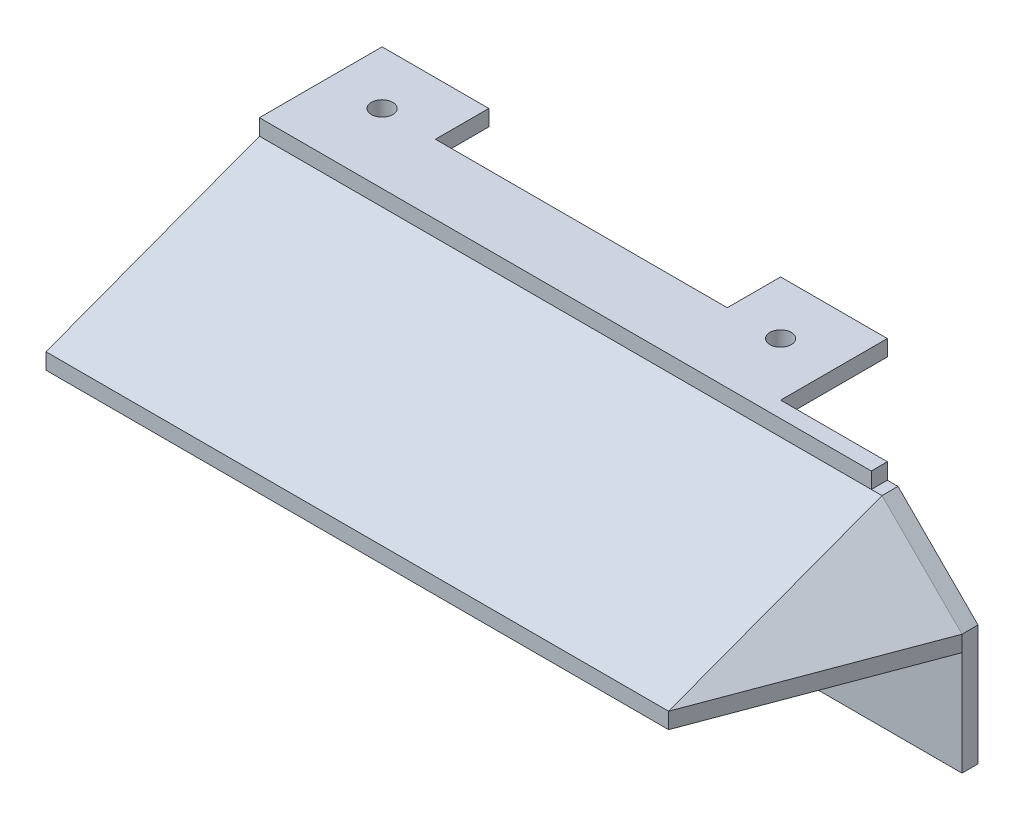
SolidWorks part; units mm, degrees
ref_plane "Plan de face" through (0, 0, 0) normal (0, 0, 1) x (1, 0, 0)
ref_plane "Plan de dessus" through (0, 0, 0) normal (0, 1, 0) x (1, 0, 0)
ref_plane "Plan de droite" through (0, 0, 0) normal (1, 0, 0) x (0, 0, -1)
sketch "Esquisse1" plane through (0, 0, 0) normal (0, 1, 0) x (1, 0, 0)
  line L0 (-37.6864, 50.2162) -> (-27.6864, 50.2162)
  line L1 (-27.6864, 50.2162) -> (-27.6864, 40.2162)
  line L2 (-27.6864, 40.2162) -> (-137.6864, 40.2162)
  line L3 (-37.6864, 50.2162) -> (-137.6864, 50.2162)
  line L4 (-137.6864, 50.2162) -> (-137.6864, 40.2162)
  line L5 (-137.6864, 50.2162) -> (-117.6864, 50.2162)
  line L6 (-122.3907, 50.2162) -> (-122.3907, 40.2162)
extrude "Boss.-Extru.1" add sketch "Esquisse1" along normal blind 3 contours L3 L6 L2 L1 L0 region at (-75.0386, 0, -45.2162)
sketch "Esquisse2" plane through (0, 0, -50.2162) normal (0, 0, -1) x (-1, 0, 0)
  line L0 (27.6864, 0) -> (27.6864, 3)
  line L1 (27.6864, 0) -> (47.6864, 0)
  line L2 (27.6864, 3) -> (47.6864, 3)
  line L3 (47.6864, 0) -> (47.6864, 3)
extrude "Boss.-Extru.2" add sketch "Esquisse2" along normal blind 10
sketch "Esquisse3" plane through (0, 3, 0) normal (0, 1, 0) x (1, 0, 0)
  line L0 (-27.6864, 50.2162) -> (-37.6864, 50.2162)
  line L1 (-27.6864, 40.2162) -> (-27.6864, 60.2162) construction
  circle A0 centre (-37.6864, 50.2162) radius 2
extrude "Enlèv. mat.-Extru.1" cut sketch "Esquisse3" against normal blind 10 contours A0 region at (-39.6298, 3, -50.2162)
sketch "Esquisse4" plane through (0, 0, -50.2162) normal (0, 0, -1) x (-1, 0, 0)
  line L0 (122.3907, 0) -> (102.3907, 0)
  line L1 (47.6864, 0) -> (122.3907, 0) construction
  line L2 (102.3907, 0) -> (102.3907, 3)
  line L3 (47.6864, 3) -> (122.3907, 3) construction
  line L4 (102.3907, 3) -> (122.3907, 3)
  line L5 (122.3907, 3) -> (122.3907, 0) construction
  line L6 (122.3907, 3) -> (122.3907, 0)
extrude "Boss.-Extru.3" add sketch "Esquisse4" along normal blind 10
sketch "Esquisse5" plane through (0, 3, 0) normal (0, 1, 0) x (1, 0, 0)
  line L0 (-102.3907, 50.2162) -> (-112.3907, 50.2162)
  circle A0 centre (-112.3907, 50.2162) radius 2
extrude "Enlèv. mat.-Extru.2" cut sketch "Esquisse5" against normal blind 20 contours A0 region at (-114.3342, 3, -50.2162)
sketch "Esquisse6" plane through (0, 0, -40.2162) normal (0, 0, 1) x (1, 0, 0)
  line L0 (-27.6864, 3) -> (-7.6864, 3)
  line L1 (-7.6864, 3) -> (-7.6864, 0)
  line L2 (-7.6864, 0) -> (-27.6864, 0)
  line L3 (-27.6864, 0) -> (-122.3907, 0)
  line L4 (-122.3907, 0) -> (-122.3907, 3)
  line L5 (-122.3907, 3) -> (-27.6864, 3)
  line L6 (-7.6864, 3) -> (-5.6864, 3)
  line L7 (-7.6864, 0) -> (-5.6864, 0)
  line L8 (-5.6864, 0) -> (-5.6864, 3)
  line L9 (-5.6864, 0) -> (9.3113, -14.9977)
  line L10 (9.3113, -14.9977) -> (9.3113, -37.5577)
  line L11 (9.3113, -37.5577) -> (-122.3907, -37.5577)
  line L12 (-122.3907, -37.5577) -> (-122.3907, 0)
  line L13 (-122.3907, 0) -> (-27.6864, 0)
  line M7 (-122.3907, 0) -> (-27.6864, 0)
  line M8 (-27.6864, 0) -> (-27.6864, 3)
  line M9 (-27.6864, 3) -> (-122.3907, 3)
  line M10 (-122.3907, 3) -> (-122.3907, 0)
extrude "Boss.-Extru.4" add sketch "Esquisse6" along normal blind 3 contours M10 M7 M8 M9 | L12 L11 L10 L9 L7 L2 M7 | L2 L1 L0 M8 region at (-75.0386, 1.5, -40.2162) region at (-17.6864, 1.5, -40.2162) region at (-57.9555, -19.0995, -40.2162)
sketch "Esquisse7" plane through (0, 0, -37.2162) normal (0, 0, 1) x (1, 0, 0)
  line L0 (9.3113, -14.9977) -> (9.3113, -17.9977)
  line L1 (9.3113, -14.9977) -> (9.3113, -37.5577) construction
  line L2 (9.3113, -17.9977) -> (-122.3907, -17.9977)
  line L3 (-122.3907, 3) -> (-122.3907, -37.5577) construction
  line L4 (-122.3907, -17.9977) -> (-122.3907, -16.4977)
  line L5 (-122.3907, -16.4977) -> (-122.3907, -14.9977)
  line L6 (-122.3907, -14.9977) -> (9.3113, -14.9977)
  line L7 (-7.6864, 0) -> (-7.6864, -17.9977)
  line L8 (-7.6864, -17.9977) -> (-7.6864, -14.9977)
  line M6 (-122.3907, 3) -> (-122.3907, -37.5577)
extrude "Boss.-Extru.5" add sketch "Esquisse7" along normal blind 40 contours L7 L6 L2 M6 region at (-65.0386, -16.4977, -37.2162)
sketch "Esquisse8" plane through (0, 0, -37.2162) normal (0, 0, 1) x (1, 0, 0)
  line L0 (-7.6864, 0) -> (-122.3907, 0)
  line L1 (-122.3907, 3) -> (-122.3907, -14.9977) construction
  line L2 (-122.3907, 0) -> (-122.3907, -3)
  line L3 (-122.3907, -3) -> (-7.6864, -3)
  line L4 (-7.6864, -3) -> (-7.6864, 0)
sketch "Esquisse9" plane through (0, -14.9977, 0) normal (0, 1, 0) x (1, 0, 0)
  line L0 (-122.3907, -2.7838) -> (-122.3907, 2.2162)
  line L1 (-122.3907, -2.7838) -> (-122.3907, 37.2162) construction
  line L2 (-7.6864, -2.7838) -> (-7.6864, 2.2162)
  line L3 (-7.6864, -2.7838) -> (-7.6864, 37.2162) construction
  line L4 (-7.6864, 2.2162) -> (-122.3907, 2.2162)
  line L5 (-122.3907, -2.7838) -> (-7.6864, -2.7838)
sketch3d "Esquisse3D1"
  line L0 (-122.3907, -14.9977, -2.2162) -> (-122.3907, -3, -37.2162)
  line L1 (-122.3907, -3, -37.2162) -> (-122.3907, 0, -37.2162)
  line L2 (-122.3907, 0, -37.2162) -> (-122.3907, -14.9977, 2.7838)
  line L3 (-122.3907, -14.9977, 2.7838) -> (-122.3907, -14.9977, -2.2162)
loft "Lissage1" add profiles "Esquisse8", "Esquisse9" connector at (-7.6864, 0, -37.2162) connector at (-7.6864, -14.9977, 2.7838)
sketch "Esquisse11" plane through (-7.6864, 0, 0) normal (1, 0, 0) x (0, 0, -1)
  line L0 (-2.7838, -17.9977) -> (37.2162, -17.9977)
  line L1 (37.2162, -17.9977) -> (37.2162, -14.9977)
  line L2 (37.2162, -14.9977) -> (2.2162, -14.9977)
  line L3 (2.2162, -14.9977) -> (37.2162, -3)
  line L4 (37.2162, -3) -> (37.2162, 0)
  line L5 (37.2162, 0) -> (-2.7838, -14.9977)
  line L6 (-2.7838, -14.9977) -> (-2.7838, -17.9977)
extrude "Boss.-Extru.6" add sketch "Esquisse11" along normal blind 2
sketch "Esquisse13" plane through (0, 0, -37.2162) normal (0, 0, 1) x (1, 0, 0)
  line L1 (9.3113, -14.9977) -> (-5.6864, 0)
  line L3 (-5.6864, -3) -> (4.9163, -14.9977)
  line L4 (4.9163, -14.9977) -> (9.3113, -14.9977)
  line L5 (-5.6864, -3) -> (-5.6864, 0)
sketch "Esquisse14" plane through (-5.6864, 0, 0) normal (1, 0, 0) x (0, 0, -1)
  line L0 (37.2162, 0) -> (-2.7838, -14.9977)
  line L1 (-2.7838, -14.9977) -> (2.2162, -14.9977)
  line L2 (2.2162, -14.9977) -> (37.2162, -3)
  line L3 (37.2162, -3) -> (37.2162, 0)
sketch3d "Esquisse3D3"
  line L0 (-5.6864, -14.9977, 2.7838) -> (9.3113, -14.9977, -37.2162)
  line L3 (4.9163, -14.9977, -37.2162) -> (-5.6864, -14.9977, -2.2162)
loft "Lissage5" add profiles "Esquisse14", "Esquisse13" connector at (-5.6864, -14.9977, -2.2162) connector at (4.9163, -14.9977, -37.2162)
sketch "Esquisse16" plane through (0, -17.9977, 0) normal (0, -1, 0) x (1, 0, 0)
  line L0 (-5.6864, -37.2162) -> (9.3113, -37.2162)
  line L1 (9.3113, -37.2162) -> (-5.6864, 2.7838)
  line L2 (-5.6864, 2.7838) -> (-5.6864, -37.2162)
extrude "Boss.-Extru.10" add sketch "Esquisse16" against normal blind 3
